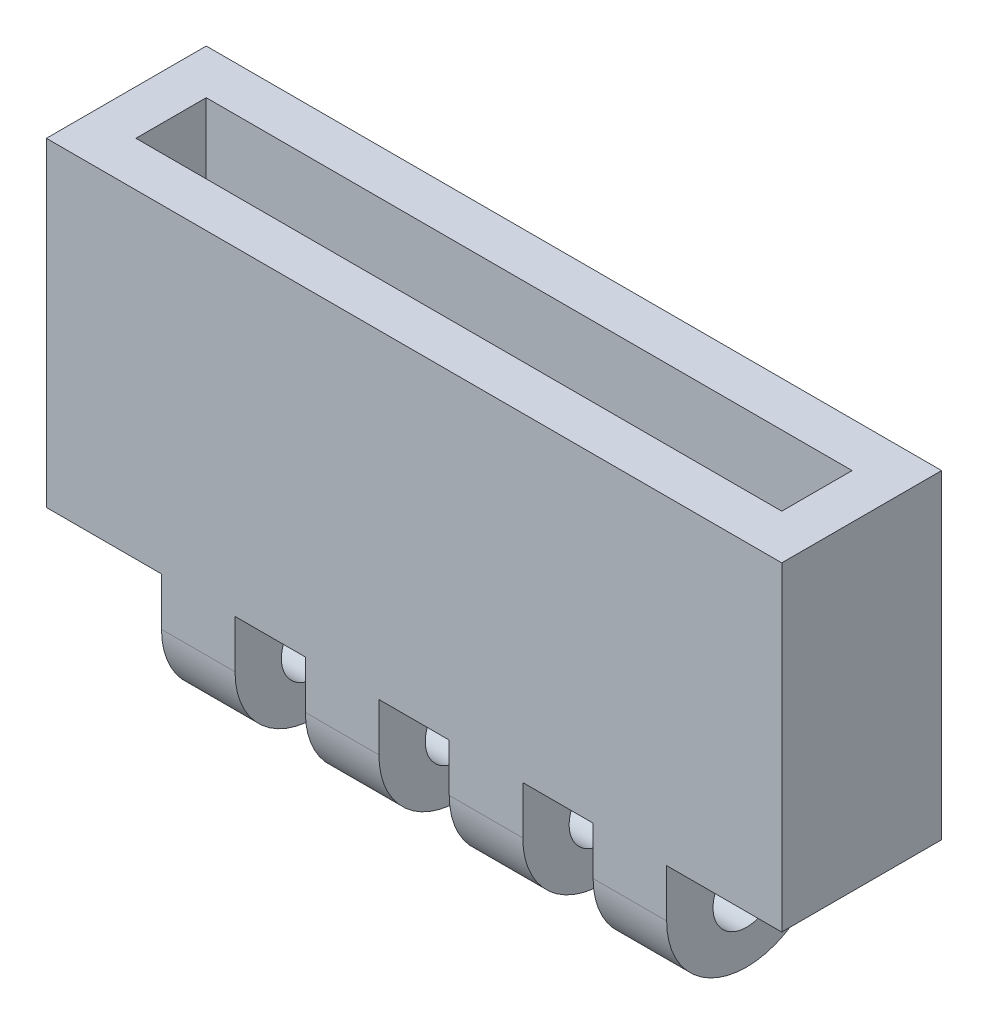
SolidWorks part; units mm, degrees
ref_plane "Front Plane" through (0, 0, 0) normal (0, 0, 1) x (1, 0, 0)
ref_plane "Top Plane" through (0, 0, 0) normal (0, 1, 0) x (1, 0, 0)
ref_plane "Right Plane" through (0, 0, 0) normal (1, 0, 0) x (0, 0, -1)
sketch "Sketch1" plane through (0, 0, 0) normal (0, 1, 0) x (1, 0, 0)
  line L1 (23, 5) -> (-23, 5)
  line L2 (23, 5) -> (23, -5)
  line L3 (23, -5) -> (-23, -5)
  line L4 (-23, 5) -> (-23, -5)
  line L5 (23, 5) -> (-23, -5) construction
  line L6 (23, -5) -> (-23, 5) construction
  point P0 (0, 0)
extrude "Boss-Extrude1" add sketch "Sketch1" along normal blind 20
sketch "Sketch2" plane through (0, 0, 0) normal (0, -1, 0) x (1, 0, 0)
  line L0 (23, -5) -> (-23, -5) construction
  line L1 (15.8, -5) -> (11.2, -5)
  line L2 (15.8, -5) -> (15.8, 5)
  line L3 (15.8, 5) -> (11.2, 5)
  line L4 (11.2, -5) -> (11.2, 5)
  line L5 (13.5, 5) -> (13.5, -5) construction
  line L6 (15.8, 0) -> (11.2, 0) construction
  line L7 (-23, 5) -> (23, 5) construction
  point P272 (13.5, 0)
  dimension "D2" = 4.6
extrude "Boss-Extrude2" add sketch "Sketch2" along normal blind 8
fillet "Fillet1" radius 5 2 edges at (13.5, -8, -5) (13.5, -8, 5)
pattern_linear "LPattern1" count 4 spacing 9 along (-1, 0, 0) of "Boss-Extrude2", "Fillet1"
sketch "Sketch4" plane through (15.8, 0, 0) normal (1, 0, 0) x (0, 0, -1)
  circle A0 centre (0, -3.74) radius 2.1
extrude "Cut-Extrude1" cut sketch "Sketch4" against normal through all
sketch "Sketch6" plane through (0, 20, 0) normal (0, 1, 0) x (1, 0, 0)
  line L0 (-23, -5) -> (23, -5) construction
  line L1 (20.2, -2.2) -> (-20.2, -2.2)
  line L2 (20.2, -2.2) -> (20.2, 2.2)
  line L3 (20.2, 2.2) -> (-20.2, 2.2)
  line L4 (-20.2, -2.2) -> (-20.2, 2.2)
  line L5 (20.2, -2.2) -> (-20.2, 2.2) construction
  line L6 (20.2, 2.2) -> (-20.2, -2.2) construction
  line L7 (-23, 5) -> (-23, -5) construction
  point P0 (0, 0)
  dimension "D1" = 2.8
  dimension "D2" = 2.8
extrude "Cut-Extrude2" cut sketch "Sketch6" against normal blind 15
